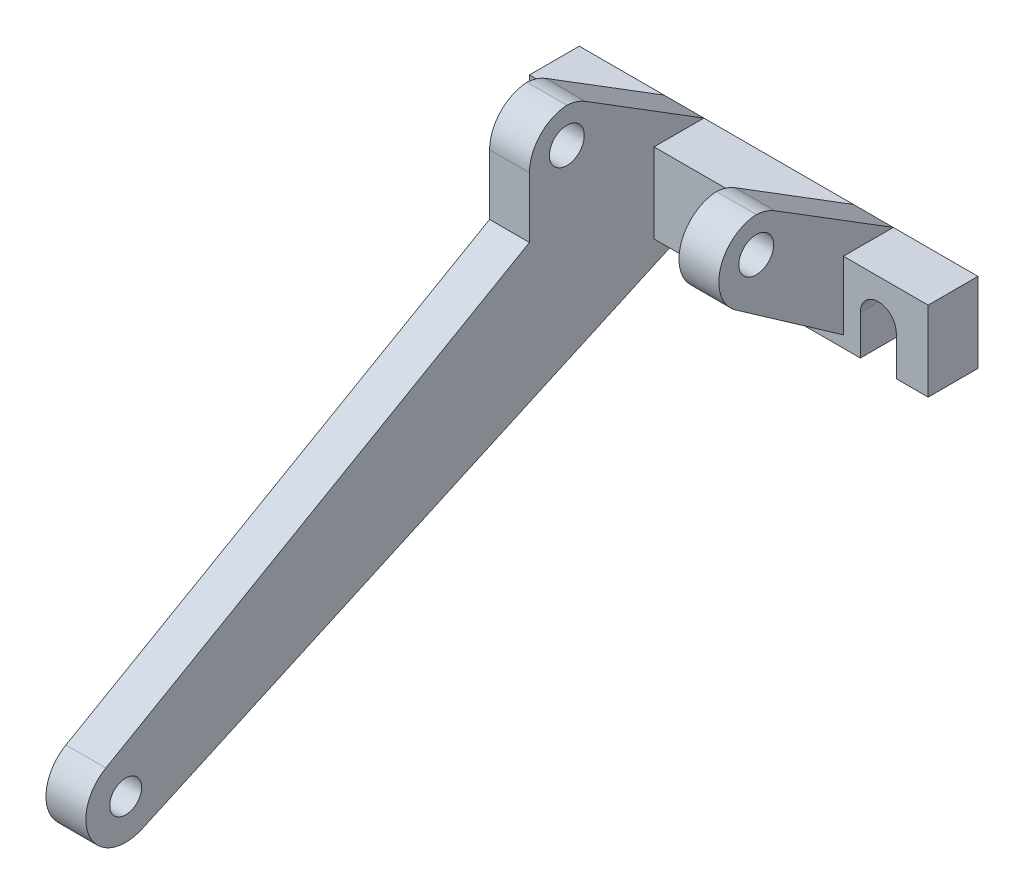
SolidWorks part; units mm, degrees
ref_plane "Front Plane" through (0, 0, 0) normal (0, 0, 1) x (1, 0, 0)
ref_plane "Top Plane" through (0, 0, 0) normal (0, 1, 0) x (1, 0, 0)
ref_plane "Right Plane" through (0, 0, 0) normal (1, 0, 0) x (0, 0, -1)
sketch "Sketch1" plane through (0, 0, 0) normal (0, 0, 1) x (1, 0, 0)
  line L0 (15, 0) -> (-15, 0) construction
  line L1 (-20, 4) -> (20, 4)
  line L2 (-20, 4) -> (-20, -4)
  line L3 (-20, -4) -> (-16.8, -4)
  line L4 (20, 4) -> (20, -4)
  line L5 (-20, 4) -> (20, -4) construction
  line L6 (-20, -4) -> (20, 4) construction
  line L7 (0, -4) -> (0, 4) construction
  line L8 (-16.8, 0) -> (-16.8, -4)
  line L9 (13.2, -4) -> (13.2, 0)
  line L10 (-13.2, -4) -> (-13.2, 0)
  line L11 (-13.2, -4) -> (13.2, -4)
  line L12 (16.8, 0) -> (16.8, -4)
  line L13 (16.8, -4) -> (20, -4)
  arc A0 (-13.2, 0) -> (-16.8, 0) centre (-15, 0) ccw
  arc A1 (13.2, 0) -> (16.8, 0) centre (15, 0) cw
  point P0 (0, 0)
  point P12 (0, 0)
  dimension "D3" = 3.6
  dimension "D1" = 40
  dimension "D2" = 8
  dimension "D4" = 15
extrude "Boss-Extrude1" add sketch "Sketch1" along normal blind 5
sketch "Sketch2" plane through (0, 0, 5) normal (0, 0, 1) x (1, 0, 0)
  line L0 (0, 4) -> (0, -4) construction
  line L1 (20, 4) -> (-20, 4) construction
  line L2 (-20, -4) -> (-16.8, -4) construction
  line L3 (11.5, -4) -> (7.5, 4) construction
  line L4 (-11.5, 4) -> (-7.5, 4)
  line L5 (-11.5, 4) -> (-11.5, -4)
  line L6 (-11.5, -4) -> (-7.5, -4)
  line L7 (-7.5, 4) -> (-7.5, -4)
  line L8 (-11.5, 4) -> (-7.5, -4) construction
  line L9 (-11.5, -4) -> (-7.5, 4) construction
  line L10 (11.5, 4) -> (7.5, -4) construction
  line L11 (7.5, 4) -> (7.5, -4)
  line L12 (11.5, -4) -> (7.5, -4)
  line L13 (11.5, 4) -> (11.5, -4)
  line L14 (11.5, 4) -> (7.5, 4)
  line L16 (-13.2, -4) -> (13.2, -4) construction
  point P6 (-9.5, 0)
  point P15 (9.5, 0)
  point P16 (0, -4)
  point P18 (0, 0)
  dimension "D1" = 7.5
  dimension "D2" = 4
extrude "Boss-Extrude2" add sketch "Sketch2" along normal blind 12.5
sketch "Sketch4" plane through (0, 4, 0) normal (0, 1, 0) x (1, 0, 0)
  line L0 (-7.5, -17.5) -> (-7.5, -5) construction
  line L1 (-11.5, -17.5) -> (-7.5, -17.5)
  line L2 (-11.5, -17.5) -> (-11.5, -10)
  line L3 (-11.5, -10) -> (-7.5, -10)
  line L4 (-7.5, -17.5) -> (-7.5, -10)
  line L5 (0, 0) -> (0, -5) construction
  line L6 (7.5, -5) -> (-7.5, -5) construction
  line L7 (7.5, -17.5) -> (7.5, -10)
  line L8 (11.5, -10) -> (7.5, -10)
  line L9 (11.5, -17.5) -> (11.5, -10)
  line L10 (11.5, -17.5) -> (7.5, -17.5)
  dimension "D1" = 7.5
extrude "Boss-Extrude3" add sketch "Sketch4" along normal blind 8
sketch "Sketch3" plane through (-11.5, 0, 0) normal (-1, 0, 0) x (0, 0, 1)
  line L0 (10, 8.5) -> (17.5, 8.5) construction
  line L4 (10, 12) -> (10, 4) construction
  line L5 (17.5, 12) -> (17.5, -4) construction
  line L6 (13.75, 8.5) -> (13.75, 12) construction
  line L7 (10, 12) -> (17.5, 12) construction
  circle A0 centre (13.75, 8.5) radius 1.75
  dimension "D1" = 3.5
  dimension "D2" = 8.5
extrude "Cut-Extrude1" cut sketch "Sketch3" against normal through all
fillet "Fillet1" radius 4 4 edges at (-9.5, 12, 10) (9.5, 12, 10) (9.5, 12, 17.5) (-9.5, 12, 17.5)
sketch "Sketch5" plane through (-7.5, 0, 0) normal (1, 0, 0) x (0, 0, -1)
  line L0 (-10, 8) -> (-10, 4) construction
  line L1 (-10, 6.5) -> (-13, 6.5)
  line L2 (-10, 6.5) -> (-10, 1.5)
  line L3 (-10, 1.5) -> (-13, 1.5)
  line L4 (-13, 6.5) -> (-13, 1.5)
  line L5 (-10, 4) -> (-5, 4) construction
  dimension "D1" = 3
  dimension "D2" = 5
  dimension "D3" = 2.5
extrude "Boss-Extrude4" [suppressed] add sketch "Sketch5" along normal up to next
sketch "Sketch6" plane through (-11.5, 0, 0) normal (-1, 0, 0) x (0, 0, 1)
  line L0 (56.0113, -29.4012) -> (11.7824, -4)
  line L1 (17.5, -4) -> (5, -4) construction
  line L2 (11.7824, -4) -> (17.5, 1.9418)
  line L3 (13.75, 8.5) -> (58.0033, -25.9326) construction
  line L4 (17.5, 1.9418) -> (59.9954, -22.4639)
  line L5 (59.9954, -22.4639) -> (56.0113, -29.4012) construction
  line L6 (13.75, 8.5) -> (13.75, -4) construction
  line L7 (17.5, 8) -> (17.5, -4) construction
  circle A0 centre (58.0033, -25.9326) radius 1.6
  arc A1 (56.0113, -29.4012) -> (59.9954, -22.4639) centre (58.0033, -25.9326) ccw
  dimension "D1" = 3.2
  dimension "D2" = 8
  dimension "D3" = 52.114
  dimension "D4" = 56.071
  dimension "D5" = 1.9676
extrude "Boss-Extrude5" add sketch "Sketch6" against normal up to surface (4 mm away) up to face at (-7.5, 6.75, 13.75)
sketch "Sketch7" plane through (-11.5, 0, 0) normal (-1, 0, 0) x (0, 0, 1)
  line L0 (1.4608, 4) -> (11.0845, 10.7386)
  line L1 (5, 4) -> (0, 4) construction
  line L2 (11.0845, 10.7386) -> (10, 4)
  line L3 (10, 8) -> (10, 4) construction
  line L4 (10, 4) -> (1.4608, 4)
  arc A0 (13.75, 11.9922) -> (10, 8) centre (14, 8) ccw construction
  dimension "D1" = 35
extrude "Boss-Extrude6" add sketch "Sketch7" against normal up to surface (4 mm away) up to face at (-7.5, -2.4438, 21.5899)
sketch "Sketch8" plane through (11.5, 0, 0) normal (1, 0, 0) x (0, 0, -1)
  line L0 (-1.4608, 4) -> (-11.0845, 10.7386)
  line L1 (-11.0845, 10.7386) -> (-10, 4)
  line L2 (-10, 4) -> (-1.4608, 4)
  arc A0 (-10, 8) -> (-13.75, 11.9922) centre (-14, 8) ccw construction
extrude "Boss-Extrude7" add sketch "Sketch8" against normal up to surface (4 mm away) up to face at (7.5, 10.25, 13.75)
sketch "Sketch9" plane through (11.5, 0, 0) normal (1, 0, 0) x (0, 0, -1)
  line L0 (-15.7943, 4.7234) -> (-5, -2.8349)
  line L1 (-5, -4) -> (-5, 4) construction
  line L2 (-5, -2.8349) -> (-5, -4)
  line L3 (-5, -4) -> (-17.5, -4)
  line L4 (-17.5, -4) -> (-17.5, 8) construction
  line L5 (-17.5, -4) -> (-5, -4) construction
  line L6 (-17.5, -4) -> (-17.5, 8)
  line L7 (-1.4608, 4) -> (-11.0845, 10.7386) construction
  arc A0 (-17.5, 8) -> (-15.7943, 4.7234) centre (-13.5, 8) ccw
  arc A1 (-13.75, 11.9922) -> (-17.5, 8) centre (-13.5, 8) ccw construction
  point P1 (0, 0)
  point P2 (-5, -4)
  point P5 (-5, -4)
extrude "Cut-Extrude2" cut sketch "Sketch9" against normal up to next
sketch "Sketch10" plane through (11.5, 0, 0) normal (1, 0, 0) x (0, 0, -1)
  line L0 (0, 4) -> (-11.8868, 11.3962)
  line L1 (-11.8868, 11.3962) -> (-5, 4)
  line L2 (-5, 4) -> (0, 4)
  arc A0 (-11.0845, 10.7386) -> (-13.75, 11.9922) centre (-14, 8) ccw construction
extrude "Boss-Extrude8" add sketch "Sketch10" against normal blind 4
ref_plane "Plane1" through (0, 0, 0) normal (-1, 0, 0) x (0, 0, 1)
mirror "Mirror1" about plane through (0, 0, 0) normal (-1, 0, 0) of "Boss-Extrude8"
sketch "Sketch11" plane through (-7.5, 0, 0) normal (1, 0, 0) x (0, 0, -1)
  line L0 (0, -4) -> (-56.3502, -29.575)
  line L1 (-56.3502, -29.575) -> (-11.7824, -4)
  line L2 (-11.7824, -4) -> (0, -4)
  line L3 (0, -4) -> (-0.1024, -3.7913)
  arc A0 (-59.9954, -22.4639) -> (-56.0113, -29.4012) centre (-58.0033, -25.9326) ccw construction
  arc M7 (-59.9954, -22.4639) -> (-56.0113, -29.4012) centre (-58.0033, -25.9326) ccw
  line M8 (-56.0113, -29.4012) -> (-11.7824, -4)
  line M9 (-11.7824, -4) -> (-5, -4)
extrude "Boss-Extrude9" add sketch "Sketch11" against normal up to surface (4 mm away) contours L2 L0 M9 M8 M7 region at (-7.5, -12.4988, 22.6531) up to face at (-11.5, -1.5669, 20.3539)
equation "\"X-ROD-SPACING\"=45"
equation "\"Y-ROD-SPACING\"=75"
equation "\"Z-ROD-SPACING\"=17.5"
equation "\"Y-BED-OFFSET\"=2"
equation "\"Y-BED-ROD-INSET\"=3.5"
equation "\"Y-BED-SCREW-SPACING\"=209"
equation "\"Y-BED-SCREW-CUTOUT-SLOT-HEIGHT\"=2.5"
equation "\"T-SLOT-NUT-FILLET-RADIUS\"=0.5"
equation "\"T-SLOT-SCREW-SHAFT-RADIUS\"=1.55"
equation "\"T-SLOT-SCREW-SHAFT-CUTOUT-LENGTH\"=11"
equation "\"T-SLOT-NUT-DEPTH\"=3.5"
equation "\"T-SLOT-NUT-WIDTH\"=2.85"
equation "\"T-SLOT-NUT-END-DISTANCE\"=8"
equation "\"ACRYLIC-THICKNESS\"=10"
equation "\"ACRYLIC-THICKNESS2\"=4.5"
equation "\"ACRYLIC-TAB-CUTOUT-SIZE\"=\"ACRYLIC-THICKNESS\"+\"ACRYLIC-TAB-TOLERANCE\"*2"
equation "\"ACRYLIC-TAB-TOLERANCE\"=-.05"
equation "\"ACRYLIC-TAB-WIDTH\"=\"ACRYLIC-THICKNESS\""
equation "\"ACRYLIC-M3-HOLE\"=2.9"
equation "\"SMOOTHROD-CAP-SCREW-DISTANCE\"=20"
equation "\"FRAME-WIDTH-INNER\"=370"
equation "\"NEMA17-HOLE-SPACING\"=31"
equation "\"NEMA17-CENTRAL-CUTOUT\"=22.5"
equation "\"Z-BRACKET-REACH\"=57"
equation "\"Z-ROD-INSET\"=13.5"
equation "\"TOP-BRACKET-SPACING\"=40"
equation "\"SMOOTHROD-X-LENGTH\"=350"
equation "\"SMOOTHROD-Y-LENGTH\"=350"
equation "\"SMOOTHROD-Z-LENGTH\"=350"
equation "\"SMOOTHROD-TIGHTENING-HEADROOM\"=.25"
equation "\"LEADSCREW-Z-LENGTH\"=300"
equation "\"SCREW-LENGTH-FRAME\"=\"ACRYLIC-THICKNESS\" + 10"
equation "\"SCREW-LENGTH-MOTOR\"=\"ACRYLIC-THICKNESS\" + 5"
equation "\"SCREW-LENGTH-EXTRUDER\"=28"
equation "\"SCREW-HEAD-RADIUS\"=6"
equation "\"PRINTED-X-SMOOTHROD-DIAMETER\"=8.8"
equation "\"PRINTED-X-SMOOTHROD-CUTOUT\"=10"
equation "\"PRINTED-X-BASE-HEIGHT\"=10"
equation "\"PRINTED-LM8UU-CUTOUT-SIZE\"=15.5"
equation "\"PRINTED-LM8UU-CUTOUT-LENGTH\"=24.5"
equation "\"PRINTED-X-IDLER-HEIGHT\"=16"
equation "\"PSU-MOUNTING-WIDTH\"=50"
equation "\"PSU-MOUNTING-HEIGHT\"=150"
equation "\"Y-BELT-TO-ROD-DISTANCE\"=20"
equation "\"SPOOL-HOLDER-ROD-SPACING\"=150"
equation "\"ACRYLIC-X-CARRIAGE-WIDTH\"=55"
equation "\"ACRYLIC-X-CARRIAGE-HEIGHT\"=75"
equation "\"ACRYLIC-X-CARRIAGE-LM8UU-CUTOUT-WIDTH\"=24.25"
equation "\"ACRYLIC-X-CARRIAGE-LM8UU-CUTOUT-HEIGHT\"=11.0"
equation "\"ACRYLIC-X-CARRIAGE-SCREW-SPACING-X\"=15"
equation "\"ACRYLIC-X-CARRIAGE-SCREW-SPACING-Y\"=33"
equation "\"ACRYLIC-X-CARRIAGE-CENTER-TAB-SPACING\"=14"
equation "\"ACRYLIC-X-CARRIAGE-EXTRUDER-OFFSET\"=26"
equation "\"ACRYLIC-X-CARRIAGE-EXTRUDER-ANGLE\"=90"
equation "\"ACRYLIC-X-CARRIAGE-EXTRUDER-SHELF-DEPTH\"=\"ACRYLIC-X-CARRIAGE-EXTRUDER-OFFSET\" + 28"
equation "\"ACRYLIC-X-CARRIAGE-EXTRUDER-BRACE-SPACING\"=23"
equation "\"ACRYLIC-X-CARRIAGE-EXTRUDER-BRACE-TAB-OFFSET\"=20"
equation "\"ACRYLIC-X-CARRIAGE-EXTRUDER-BRACE-HEIGHT\"=35"
equation "\"ACRYLIC-X-CARRIAGE-EXTRUDER-BRACE-SCREW-SPACING\"=22"
equation "\"ACRYLIC-X-CARRIAGE-DUAL-WIDTH-MULTIPLIER\"=1.65"
equation "\"ACRYLIC-X-CARRIAGE-DUAL-HOTEND-SPACING\"=42"
equation "\"ACRYLIC-X-CARRIAGE-DUAL-WIDTH\"=75"
equation "\"ACRYLIC-X-CARRIAGE-DUAL-HOTEND-SEPARATION\"=36"
equation "\"ACRYLIC-X-CARRIAGE-DUAL-MOUNT-PLATE-DEPTH\"=75"
equation "\"ACRYLIC-X-CARRIAGE-DUAL-MOUNT-BRACE-WIDTH\"=33"
equation "\"ACRYLIC-X-CARRIAGE-DUAL-MOUNT-SCREW-WIDTH\"=40"
equation "\"D3@Sketch1\"=3.6"
equation "\"PRINTED-M3-HOLE\"=3.5"
equation "\"BLOWER-FAN-WIDTH\"=15"
equation "\"D1@Sketch2\"=\"BLOWER-FAN-WIDTH\"/2"
